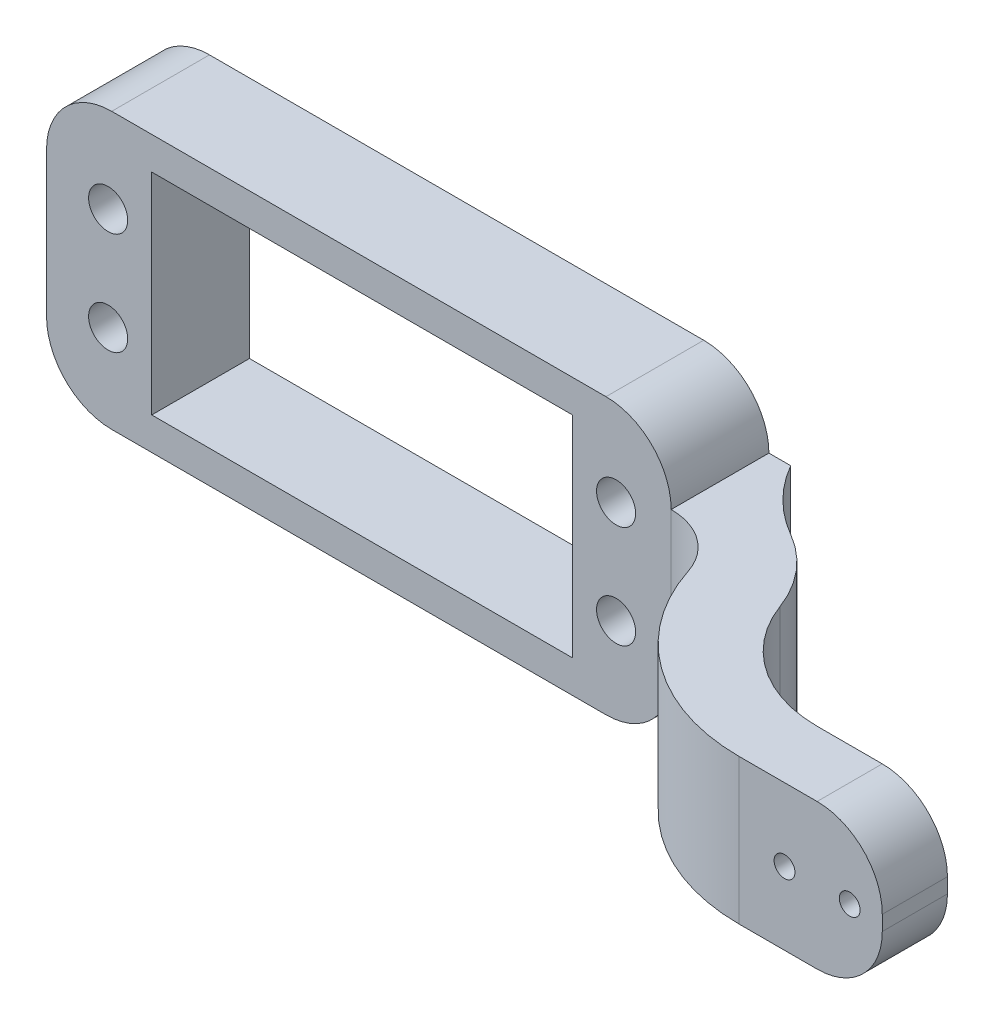
SolidWorks part; units mm, degrees
ref_plane "Front Plane" through (0, 0, 0) normal (0, 0, 1) x (1, 0, 0)
ref_plane "Top Plane" through (0, 0, 0) normal (0, 1, 0) x (1, 0, 0)
ref_plane "Right Plane" through (0, 0, 0) normal (1, 0, 0) x (0, 0, -1)
sketch "Sketch2" plane through (0, 0, 0) normal (0, 0, 1) x (1, 0, 0)
  line L0 (0, 10.25) -> (0, 5) construction
  line L1 (20.5, 10.25) -> (-20.5, 10.25) construction
  line L2 (20.5, 10.25) -> (20.5, -10.25) construction
  line L3 (20.5, -10.25) -> (-20.5, -10.25) construction
  line L4 (-20.5, 10.25) -> (-20.5, -10.25) construction
  line L5 (20.5, 10.25) -> (-20.5, -10.25) construction
  line L6 (20.5, -10.25) -> (-20.5, 10.25) construction
  line L7 (-24.75, 5) -> (24.75, 5) construction
  line L8 (-24.75, 5) -> (-24.75, -5) construction
  line L9 (-24.75, -5) -> (24.75, -5) construction
  line L10 (24.75, 5) -> (24.75, -5) construction
  line L11 (-24.75, 0) -> (-20.5, 0) construction
  line L12 (23.7659, 13.425) -> (-24.4, 13.425)
  line L13 (23.7659, -13.425) -> (-24.4, -13.425)
  line L14 (-30.75, 7.075) -> (-30.75, -7.075)
  line L15 (30.1159, -7.075) -> (30.1159, 7.075)
  circle A0 centre (-24.75, 5) radius 2.5 construction
  circle A1 centre (-24.75, -5) radius 2.5 construction
  circle A2 centre (24.75, 5) radius 2.5 construction
  circle A3 centre (24.75, -5) radius 2.5 construction
  arc A4 (-30.75, -7.075) -> (-24.4, -13.425) centre (-24.4, -7.075) ccw
  arc A5 (-24.4, 13.425) -> (-30.75, 7.075) centre (-24.4, 7.075) ccw
  arc A6 (23.7659, -13.425) -> (30.1159, -7.075) centre (23.7659, -7.075) ccw
  arc A7 (23.7659, 13.425) -> (30.1159, 7.075) centre (23.7659, 7.075) cw
  point P0 (0, 0)
  dimension "D7" = 5
  dimension "D9" = 6.35
  dimension "D1" = 20.5
  dimension "D2" = 41
  dimension "D3" = 49.5
  dimension "D4" = 10
  dimension "D5" = 3.175
  dimension "D6" = 3.175
  dimension "D8" = 6
extrude "Boss-Extrude1" add sketch "Sketch2" along normal mid plane 30.353
sketch "Sketch3" plane through (0, 0, 15.1765) normal (0, 0, 1) x (1, 0, 0)
  line L0 (-20.5, 10.25) -> (-20.5, -10.25)
  line L1 (-20.5, -10.25) -> (20.5, -10.25)
  line L2 (20.5, -10.25) -> (20.5, 10.25)
  line L3 (20.5, 10.25) -> (-20.5, 10.25)
extrude "Cut-Extrude1" cut sketch "Sketch3" against normal offset from surface (27.178 mm away) 3.175 up to face at (-0.3171, 0, -15.1765)
sketch "Sketch4" plane through (0, 0, 15.1765) normal (0, 0, 1) x (1, 0, 0)
  circle A0 centre (-24.75, 5) radius 1.905
  circle A1 centre (-24.75, -5) radius 1.905
  circle A2 centre (24.75, -5) radius 1.905
  circle A3 centre (24.75, 5) radius 1.905
  dimension "D1" = 3.81
extrude "Cut-Extrude2" cut sketch "Sketch4" against normal blind 12.7
sketch "Sketch5" plane through (-30.75, 0, 0) normal (-1, 0, 0) x (0, 0, 1)
  line L0 (-10.3505, -13.425) -> (-10.3505, 13.425) construction
  line L1 (-10.3505, 4.7625) -> (-4.0005, 4.7625)
  line L2 (-10.3505, 4.7625) -> (-10.3505, -4.7625)
  line L3 (-10.3505, -4.7625) -> (-4.0005, -4.7625)
  line L4 (-4.0005, 4.7625) -> (-4.0005, -4.7625)
  line L7 (15.1765, 13.425) -> (-15.1765, 13.425) construction
  line L8 (15.1765, -13.425) -> (-15.1765, -13.425) construction
  line L9 (-15.1765, 7.075) -> (-15.1765, -7.075) construction
  point P9 (-10.3505, 0)
  dimension "D1" = 9.525
  dimension "D2" = 6.35
  dimension "D3" = 4.826
extrude "Cut-Extrude3" cut sketch "Sketch5" against normal up to surface (10.25 mm away) up to face at (-20.5, 0, 1.5875)
sketch "Sketch7" plane through (0, 0, 15.1765) normal (0, 0, 1) x (1, 0, 0)
  line L0 (30.1159, 7.075) -> (30.1159, -7.075)
  line L1 (30.1159, 7.075) -> (68.2159, 7.075)
  line L3 (30.1159, -7.075) -> (68.2159, -7.075)
  line L4 (68.2159, 7.075) -> (68.2159, -7.075)
  line L5 (30.1159, 7.075) -> (28.6967, 7.075)
  line L6 (30.1159, 7.075) -> (30.1159, -7.075)
  line L7 (30.1159, -7.075) -> (28.6967, -7.075)
  line L8 (28.6967, 7.075) -> (28.6967, -7.075)
  line L9 (68.2159, 0) -> (28.6967, 0) construction
  circle A0 centre (65.0409, 0) radius 1.016
  circle A1 centre (58.6909, 0) radius 1.016
  line M17 (30.1159, -7.075) -> (30.1159, 7.075)
  dimension "D2" = 2.032
  dimension "D3" = 6.35
  dimension "D4" = 3.175
  dimension "D1" = 38.1
extrude "Boss-Extrude2" add sketch "Sketch7" along normal blind 17.526 and the other way blind 1.5875 separate body contours L4 L1 L3 M17 | L9 L4 L1 L6 A1 A0 region at (49.0112, 3.5753, 15.1765) region at (49.0112, -3.5753, 15.1765)
combine bodies "Combine1" operation type add bodies to combine 105 104
fillet "Fillet3" radius 15.875 1 edges at (30.1159, 0, 13.589)
fillet "Fillet4" radius 6.35 2 edges at (68.2159, -7.075, 23.1457) (68.2159, 7.075, 23.1457)
sketch "Sketch9" plane through (0, 7.075, 0) normal (0, 1, 0) x (1, 0, 0)
  line L1 (30.1159, -32.7025) -> (61.8659, -32.7025) construction
  line L2 (54.2646, -32.7025) -> (24.8898, -36.8503)
  line L3 (24.8898, -36.8503) -> (30.1159, -15.1765)
  line L4 (23.7659, -15.1765) -> (-24.4, -15.1765) construction
  line L5 (54.2646, -32.7025) -> (61.8659, -32.7025)
  line L7 (55.5159, -26.3525) -> (68.2159, -26.3525) construction
  line L10 (59.5029, -4.7266) -> (70.2622, -12.046)
  line L12 (68.2159, -13.589) -> (68.2159, -32.7025) construction
  line L13 (55.5159, -26.3525) -> (68.2159, -26.3525)
  line L14 (68.2159, -26.3525) -> (70.2622, -12.046)
  line L15 (59.5029, -4.7266) -> (42.7981, -7.2885)
  line L16 (42.7981, -7.2885) -> (38.0454, -11.4575)
  arc A0 (30.1159, -15.1765) -> (36.1531, -19.558) centre (30.1159, -21.5265) cw
  arc A1 (36.1531, -19.558) -> (54.2646, -32.7025) centre (54.2646, -13.6525) ccw
  arc A2 (38.0454, -11.4575) -> (43.6024, -18.0524) centre (31.6889, -22.4523) cw
  arc A3 (43.6024, -18.0524) -> (55.5159, -26.3525) centre (55.5159, -13.6525) ccw
  arc A4 (30.1159, 2.286) -> (45.9909, -13.589) centre (45.9909, 2.286) ccw construction
  arc A5 (30.1159, 2.286) -> (45.9909, -13.589) centre (45.9909, 2.286) ccw construction
  point P27 (0, 0)
  point P28 (0, 0)
  point P29 (39.8244, -13.2316)
  point P30 (63.3579, -5.814)
  point P31 (41.8632, -32.7025)
  point P32 (41.8632, -32.7025)
  point P33 (35.9895, -24.0279)
  point P34 (48.8772, -32.7025)
  point P35 (40.3774, -24.0279)
  point P36 (30.1159, -15.1765)
  point P37 (39.7103, -24.0279)
  point P38 (38.236, -22.7669)
  line M3 (30.1159, -32.7025) -> (61.8659, -32.7025)
  line M4 (61.8659, -32.7025) -> (61.8659, -13.589)
  line M5 (61.8659, -13.589) -> (45.9909, -13.589)
  line M8 (30.1159, -15.1765) -> (30.1159, -32.7025)
  dimension "D3" = 12.7
  dimension "D4" = 6.35
  dimension "D5" = 19.05
  dimension "D1" = 6.35
  dimension "D2" = 12.7
extrude "Cut-Extrude4" cut sketch "Sketch9" against normal through all contours A1 A0 M8 M3 | L3 L2 M3 M8 | A3 L10 M4 | A2 A3 M4 M5 region at (55.8608, 7.075, 15.7354) region at (35.8805, 7.075, 26.3311) region at (39.5261, 7.075, 34.4149)
sketch "Sketch11" plane through (0, 0, -15.1765) normal (0, 0, -1) x (-1, 0, 0)
  line L1 (80.5295, -45.8253) -> (-80.5295, -45.8253)
  line L2 (80.5295, -45.8253) -> (80.5295, 45.8253)
  line L3 (80.5295, 45.8253) -> (-80.5295, 45.8253)
  line L4 (-80.5295, -45.8253) -> (-80.5295, 45.8253)
  line L5 (80.5295, -45.8253) -> (-80.5295, 45.8253) construction
  line L6 (80.5295, 45.8253) -> (-80.5295, -45.8253) construction
  point P0 (0, 0)
extrude "Cut-Extrude5" cut sketch "Sketch11" against normal offset from surface (20.828 mm away) 9.525 up to face at (26.655, 5, 15.1765)
